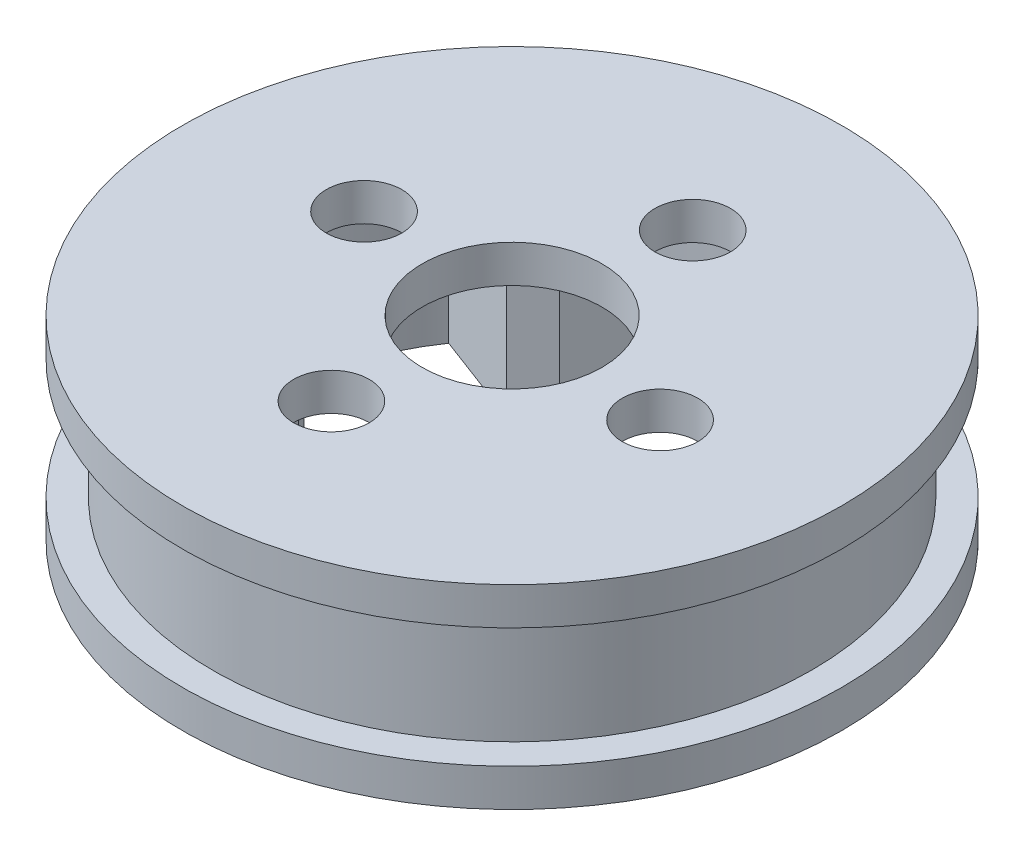
SolidWorks part; units mm, degrees
ref_plane "Front Plane" through (0, 0, 0) normal (0, 0, 1) x (1, 0, 0)
ref_plane "Top Plane" through (0, 0, 0) normal (0, 1, 0) x (1, 0, 0)
ref_plane "Right Plane" through (0, 0, 0) normal (1, 0, 0) x (0, 0, -1)
sketch "Sketch1" plane through (0, -4.6409, 0) normal (0, -1, 0) x (1, 0, 0)
  circle A0 centre (57.8368, 11.7553) radius 1.6 construction
  circle A1 centre (57.8368, 11.7553) radius 1.6
  circle A2 centre (65.4942, 5.4812) radius 1.6 construction
  circle A3 centre (64.1109, 19.4127) radius 1.6 construction
  circle A4 centre (71.7683, 13.1385) radius 1.6 construction
  circle A5 centre (65.4942, 5.4812) radius 1.6
  circle A6 centre (64.1109, 19.4127) radius 1.6
  circle A7 centre (71.7683, 13.1385) radius 1.6
  circle A8 centre (64.8026, 12.4469) radius 13.97
  circle A9 centre (64.8026, 12.4469) radius 3.81
  dimension "D1" = 27.94
  dimension "D2" = 7.62
extrude "Boss-Extrude1" add sketch "Sketch1" along normal blind 1.5875
sketch "Sketch2" plane through (0, -6.2284, 0) normal (0, -1, 0) x (1, 0, 0)
  circle A0 centre (64.8026, 12.4469) radius 12.7
  circle A2 centre (57.8368, 11.7553) radius 3.175 construction
  circle A3 centre (64.1109, 19.4127) radius 3.175 construction
  circle A4 centre (71.7683, 13.1385) radius 3.175 construction
  circle A5 centre (65.4942, 5.4812) radius 3.175 construction
  circle A6 centre (64.8026, 12.4469) radius 10.414
  dimension "D1" = 25.4
  dimension "D2" = 6.35
  dimension "D3" = 2.286
extrude "Boss-Extrude2" add sketch "Sketch2" along normal blind 5.08
sketch "Sketch3" plane through (0, -11.3084, 0) normal (0, -1, 0) x (1, 0, 0)
  circle A0 centre (64.8026, 12.4469) radius 13.97 construction
  circle A1 centre (64.8026, 12.4469) radius 13.97
  circle A2 centre (64.8026, 12.4469) radius 10.414 construction
  circle A3 centre (64.8026, 12.4469) radius 10.414
extrude "Boss-Extrude3" add sketch "Sketch3" along normal blind 1.5875
sketch "Sketch4" plane through (0, -6.2284, 0) normal (0, -1, 0) x (1, 0, 0)
  line L0 (55.2271, 16.541) -> (59.3877, 15.8574)
  line L1 (59.3877, 15.8574) -> (60.3938, 17.0854)
  line L2 (60.3938, 17.0854) -> (58.9055, 21.0304)
  line L3 (64.8026, 12.4469) -> (56.7472, 19.0471) construction
  line L4 (64.8026, 12.4469) -> (64.1109, 19.4127) construction
  line L5 (68.8966, 22.0224) -> (68.2131, 17.8618)
  line L6 (69.4411, 16.8556) -> (73.386, 18.344)
  line L7 (64.8026, 12.4469) -> (71.4028, 20.5023) construction
  line L8 (68.2131, 17.8618) -> (69.4411, 16.8556)
  line L9 (74.3781, 8.3528) -> (70.2174, 9.0364)
  line L10 (69.2113, 7.8084) -> (70.6997, 3.8634)
  line L11 (64.8026, 12.4469) -> (72.8579, 5.8467) construction
  line L12 (70.2174, 9.0364) -> (69.2113, 7.8084)
  line L13 (60.7085, 2.8714) -> (61.392, 7.032)
  line L14 (60.1641, 8.0382) -> (56.2191, 6.5498)
  line L15 (64.8026, 12.4469) -> (58.2024, 4.3916) construction
  line L16 (61.392, 7.032) -> (60.1641, 8.0382)
  arc A0 (73.386, 18.344) -> (68.8966, 22.0224) centre (64.8026, 12.4469) ccw
  circle A1 centre (64.8026, 12.4469) radius 10.414
  arc A2 (58.9055, 21.0304) -> (55.2271, 16.541) centre (64.8026, 12.4469) ccw
  arc A3 (70.6997, 3.8634) -> (74.3781, 8.3528) centre (64.8026, 12.4469) ccw
  arc A4 (56.2191, 6.5498) -> (60.7085, 2.8714) centre (64.8026, 12.4469) ccw
  point P9 (59.8908, 16.4714)
  point P28 (64.8026, 12.4469)
  dimension "D2" = 45
  dimension "D3" = 6.35
  dimension "D4" = 120
  dimension "D5" = 1.5875
  dimension "D1" = 0
  dimension "D6" = 4
extrude "Boss-Extrude4" add sketch "Sketch4" along normal up to surface (6.6675 mm away) up to face at (78.7726, -12.8959, 12.4469)
